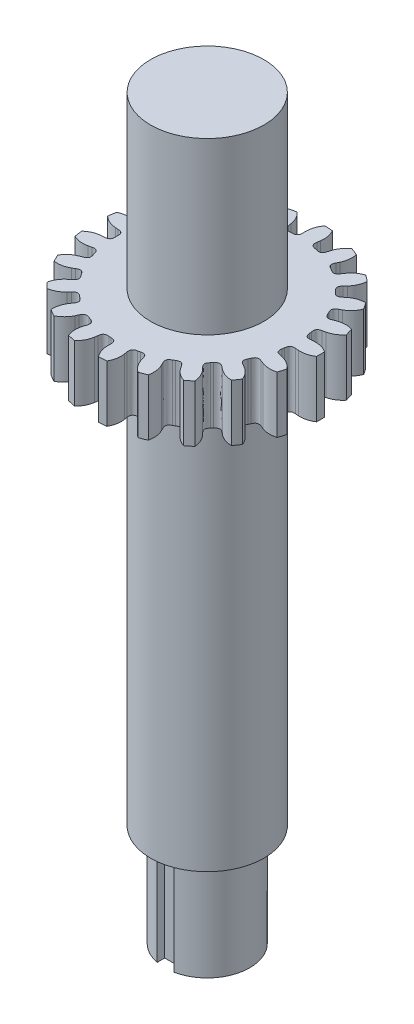
SolidWorks part; units mm, degrees
ref_plane "Front Plane" through (0, 0, 0) normal (0, 0, 1) x (1, 0, 0)
ref_plane "Top Plane" through (0, 0, 0) normal (0, 1, 0) x (1, 0, 0)
ref_plane "Right Plane" through (0, 0, 0) normal (1, 0, 0) x (0, 0, -1)
sketch "Sketch1" plane through (0, 0, 0) normal (0, 1, 0) x (1, 0, 0)
  line L0 (0, 0) -> (163.1522, 0) construction
  line L1 (0, 0) -> (160.0238, 12.5941) construction
  line L2 (0, 0) -> (159.4762, 28.12) construction
  line L3 (0, 0) -> (167.8358, 5.861) construction
  line L4 (0, 0) -> (15.7569, 2.7784)
  line L5 (15.9507, 1.2553) -> (17.4461, 1.373)
  line L6 (0, 0) -> (15.7569, -2.7784)
  line L7 (15.9507, -1.2553) -> (17.4461, -1.373)
  circle A1 centre (0, 0) radius 17.5 construction
  circle A2 centre (0, 0) radius 16 construction
  circle A3 centre (0, 0) radius 20 construction
  arc A4 (15.7569, 2.7784) -> (15.9507, 1.2553) centre (0, 0) cw
  arc A5 (19.9878, 0.698) -> (19.9878, -0.698) centre (0, 0) cw
  arc A6 (17.4461, 1.373) -> (19.9878, 0.698) centre (17.7571, -2.5787) cw
  arc A7 (15.7569, -2.7784) -> (15.9507, -1.2553) centre (0, 0) ccw
  arc A8 (17.4461, -1.373) -> (19.9878, -0.698) centre (17.7571, 2.5787) ccw
  dimension "D4" = 40
  dimension "D5" = 35
  dimension "D6" = 32
  dimension "D1" = 2
  dimension "D2" = 4.5
  dimension "D3" = 10
extrude "Boss-Extrude1" add sketch "Sketch1" along normal mid plane 10
fillet "Fillet1" radius 1 2 edges at (15.9507, 0, -1.2553) (15.9507, 0, 1.2553) curvature continuous yes
pattern_circular "CirPattern1" count 21 over 360 about axis through (0, 5, 0) along (0, -1, 0) of "Boss-Extrude1", "Fillet1"
sketch "Sketch3" plane through (0, 5, 0) normal (0, 1, 0) x (1, 0, 0)
  circle A0 centre (0, 0) radius 10
  dimension "D1" = 20
extrude "Boss-Extrude2" add sketch "Sketch3" along normal blind 30 and the other way blind 100
sketch "Sketch4" plane through (0, -95, 0) normal (0, -1, 0) x (1, 0, 0)
  circle A0 centre (0, 0) radius 7.5
  dimension "D1" = 15
extrude "Cut-Extrude1" cut sketch "Sketch4" against normal blind 18 flip side to cut
sketch "Sketch5" plane through (0, -95, 0) normal (0, -1, 0) x (1, 0, 0)
  line L1 (1.5, 9) -> (-1.5, 9)
  line L2 (1.5, 9) -> (1.5, 6)
  line L3 (1.5, 6) -> (-1.5, 6)
  line L4 (-1.5, 9) -> (-1.5, 6)
  line L5 (1.5, 9) -> (-1.5, 6) construction
  line L6 (1.5, 6) -> (-1.5, 9) construction
  circle A0 centre (0, 0) radius 7.5 construction
  circle A1 centre (0, 0) radius 7.5 construction
  point P0 (0, 7.5)
  point P9 (0, 0)
  point P11 (0, 0)
  dimension "D1" = 3
extrude "Cut-Extrude2" cut sketch "Sketch5" against normal up to surface (18 mm away) up to face at (0, -77, -10)
